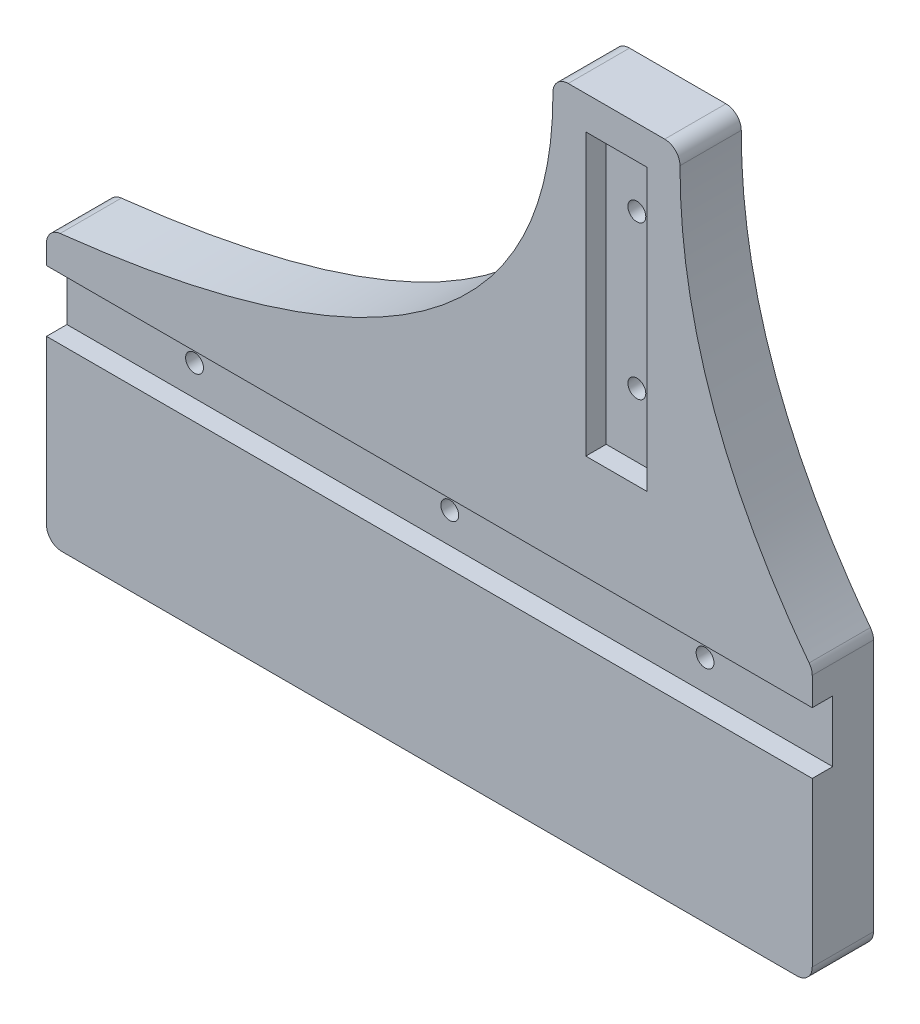
SolidWorks part; units mm, degrees
ref_plane "Ebene vorne" through (0, 0, 0) normal (0, 0, 1) x (1, 0, 0)
ref_plane "Ebene oben" through (0, 0, 0) normal (0, 1, 0) x (1, 0, 0)
ref_plane "Ebene rechts" through (0, 0, 0) normal (1, 0, 0) x (0, 0, -1)
sketch "Skizze1" plane through (0, 0, 0) normal (0, 0, 1) x (1, 0, 0)
  line L0 (24.14, 88) -> (49.14, 88)
  line L3 (75, 12.5) -> (75, -41)
  line L4 (75, -41) -> (-75, -41)
  line L9 (-75, -41) -> (-75, 12.5)
  line L13 (30.64, 81.5) -> (42.64, 81.5)
  line L14 (30.64, 81.5) -> (30.64, 26.5)
  line L15 (30.64, 26.5) -> (42.64, 26.5)
  line L16 (42.64, 81.5) -> (42.64, 26.5)
  line L17 (30.64, 81.5) -> (42.64, 26.5) construction
  line L18 (30.64, 26.5) -> (42.64, 81.5) construction
  line L19 (-75, 6) -> (75, 6)
  line L20 (-75, 6) -> (-75, -6)
  line L21 (-75, -6) -> (75, -6)
  line L22 (75, 6) -> (75, -6)
  line L23 (-75, 6) -> (75, -6) construction
  line L24 (-75, -6) -> (75, 6) construction
  line L26 (-75, 12.5) -> (75, 12.5) construction
  line L27 (24.14, 81.5) -> (49.14, 81.5) construction
  line L28 (-50, 0) -> (50, 0) construction
  line L29 (36.64, 69) -> (36.64, 39) construction
  circle A0 centre (-50, 0) radius 1.75
  circle A1 centre (0, 0) radius 1.75
  circle A2 centre (50, 0) radius 1.75
  circle A3 centre (36.64, 69) radius 1.75
  circle A4 centre (36.64, 39) radius 1.75
  spline S0 degree 2 poles (24.14, 88) (26.8075, 22.9626) (-75, 12.5) knots 0 0 0 1 1 1
  spline S1 degree 2 poles (49.14, 88) (47.9994, 47.6999) (75, 12.5) knots 0 0 0 1 1 1
  point P2 (0, -41)
  point P13 (36.64, 88)
  point P16 (36.64, 54)
  point P23 (0, 0)
  point P33 (0, 0)
  point P34 (36.64, 54)
  dimension "D12" = 3.5
  dimension "D13" = 3.5
  dimension "D14" = 3.5
  dimension "D15" = 3.5
  dimension "D16" = 3.5
  dimension "D2" = 25
  dimension "D3" = 150
  dimension "D4" = 35
  dimension "D5" = 36.64
  dimension "D6" = 6.5
  dimension "D7" = 69
  dimension "D8" = 6.5
  dimension "D9" = 12
  dimension "D10" = 55
  dimension "D11" = 12
  dimension "D17" = 100
  dimension "D18" = 30
extrude "Aufsatz-Linear austragen1" add sketch "Skizze1" against normal blind 12 contours S1 L0 S0 L9 L19 L3 L13 L16 L15 L14 | L16 L13 L14 L15 | L9 L21 L3 L19 | L21 L9 L4 L3 region at (18.2385, 29.5651, 0) region at (0, 4.4952, 0) region at (0, -23.5, 0) region at (36.64, 54, 0)
extrude "Schnitt-Linear austragen2" cut sketch "Skizze1<4>" against normal blind 4 contours L16 L13 L14 L15 | L20 L19 L22 L21 region at (36.64, 54, 0)
sketch "Skizze1<4>" plane through (0, 0, 0) normal (0, 0, 1) x (1, 0, 0) same geometry as "Skizze1"
fillet "Verrundung1" radius 3 6 edges at (75, -41, -6) (75, 12.5, -6) (49.14, 88, -6) (-75, -41, -6) (-75, 12.5, -6) (24.14, 88, -6)
